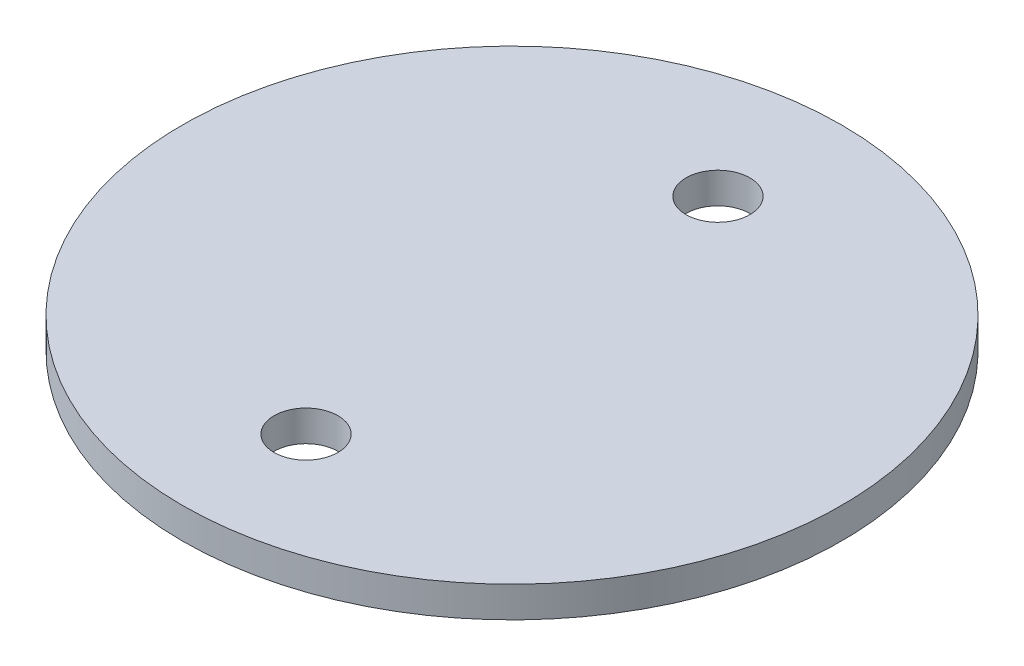
SolidWorks part; units mm, degrees
ref_plane "Front Plane" through (0, 0, 0) normal (0, 0, 1) x (1, 0, 0)
ref_plane "Top Plane" through (0, 0, 0) normal (0, 1, 0) x (1, 0, 0)
ref_plane "Right Plane" through (0, 0, 0) normal (1, 0, 0) x (0, 0, -1)
sketch "Sketch1" plane through (0, 0, 0) normal (0, 1, 0) x (1, 0, 0)
  line L0 (0, -20) -> (0, 20)
  circle A0 centre (0, 0) radius 32
  circle A1 centre (0, 20) radius 3.1
  circle A2 centre (0, -20) radius 3.1
  point P6 (0, 0)
  dimension "D1" = 64
  dimension "D3" = 6.2
  dimension "D2" = 40
extrude "Boss-Extrude1" add sketch "Sketch1" along normal blind 3 contours A0 A2 A1 region at (-31.0949, 0, 0)
